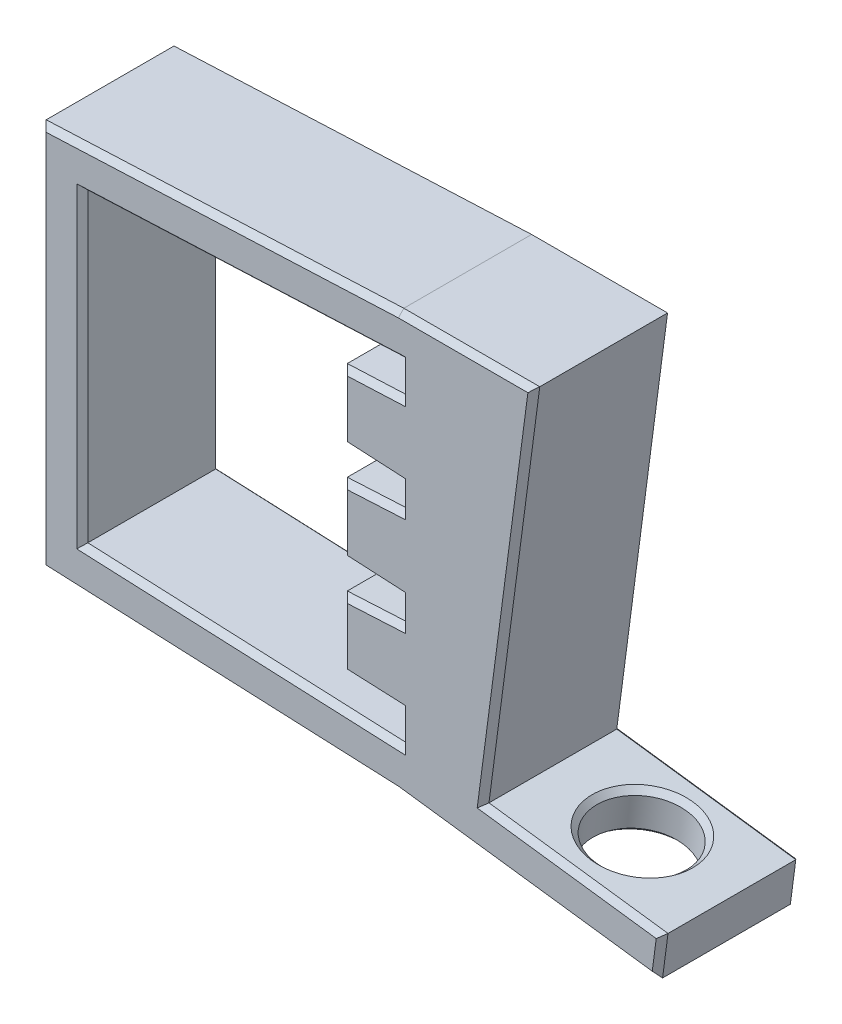
SolidWorks part; units mm, degrees
ref_plane "Top" through (0, 0, 0) normal (0, 0, 1) x (1, 0, 0)
ref_plane "Front" through (0, 0, 0) normal (0, 1, 0) x (1, 0, 0)
ref_plane "Right" through (0, 0, 0) normal (1, 0, 0) x (0, 0, -1)
sketch "Sketch1" plane through (0, 0, 0) normal (0, 0, 1) x (1, 0, 0)
  line L0 (0, 0) -> (22.8782, -0.9989)
  line L1 (-3, -2.8719) -> (22.7473, -3.996)
  line L2 (0, 0) -> (0, 22)
  line L3 (0, 22) -> (22.8782, 22.9989)
  line L4 (-3, -2.8719) -> (-3, 24.8719)
  line L5 (-3, 24.8719) -> (22.7473, 25.996)
  line L9 (22.8782, -0.9989) -> (22.8782, 1.3011)
  line L10 (22.8782, 1.3011) -> (18.6782, 1.4845)
  line L11 (18.6782, 1.4845) -> (18.6782, 6.3347)
  line L12 (18.6782, 6.3347) -> (22.8782, 6.5548)
  line L13 (22.8782, 6.5548) -> (22.8782, 8.3548)
  line L14 (22.8782, 8.3548) -> (18.6782, 8.5749)
  line L15 (18.6782, 8.5749) -> (18.6782, 13.4251)
  line L20 (22.8782, 22.9989) -> (22.8782, 20.6989)
  line L21 (22.8782, 20.6989) -> (18.6782, 20.5155)
  line L22 (18.6782, 20.5155) -> (18.6782, 15.6653)
  line L23 (18.6782, 15.6653) -> (22.8782, 15.4452)
  line L24 (22.8782, 15.4452) -> (22.8782, 13.6452)
  line L25 (22.8782, 13.6452) -> (18.6782, 13.4251)
  line L26 (22.7473, -3.996) -> (41.3754, -6.4485)
  line L27 (41.3754, -6.4485) -> (41.767, -3.4741)
  line L28 (41.767, -3.4741) -> (28.8782, -1.7773)
  line L29 (28.8782, -1.7773) -> (32.5346, 25.996)
  line L30 (32.5346, 25.996) -> (22.7473, 25.996)
  point P3 (0, 0)
  dimension "D1" = 92.5
  dimension "D2" = 92.5
  dimension "D3" = 22
  dimension "D4" = 22.9
  dimension "D6" = 90
  dimension "D8" = 92.5
  dimension "D9" = 93
  dimension "D10" = 93
  dimension "D11" = 1.8
  dimension "D12" = 2.3
  dimension "D13" = 3
  dimension "D14" = 13
  dimension "D15" = 82.5
  dimension "D16" = 2.3
  dimension "D17" = 1.8
  dimension "D18" = 6
  dimension "D19" = 4.2
  dimension "D5" = 3
extrude "Boss-Extrude1" add sketch "Sketch1" along normal blind 10
sketch "Sketch2" plane through (-2.6361, 2.3717, 0) normal (0.1305, 0.9914, 0) x (0.9914, -0.1305, 0)
  line L0 (31.7863, -10) -> (31.7863, 0) construction
  line L3 (25.9975, 0) -> (44.7863, 0) construction
  circle A1 centre (38.2863, -5) radius 3.25
  dimension "D3" = 6.5
  dimension "D1" = 5
  dimension "D2" = 6.5
extrude "Cut-Extrude1" cut sketch "Sketch2" against normal blind 10
chamfer "Chamfer1" distance 0.4 angle 45 50 edges at (22.8782, 0.1511, 10) (20.7782, 1.3928, 10) (18.6782, 3.9096, 10) (20.7782, 6.4447, 10) (22.8782, 7.4548, 10) (20.7782, 8.4648, 10) (18.6782, 11, 10) (20.7782, 13.5352, 10) (22.8782, 14.5452, 10) (20.7782, 15.5553, 10) (18.6782, 18.0904, 10) (20.7782, 20.6072, 10) (22.8782, 21.8489, 10) (11.4391, 22.4994, 10) (0, 11, 10) (11.4391, -0.4994, 10) (9.8737, 25.434, 10) (27.641, 25.996, 10) (30.7064, 12.1094, 10) (35.3226, -2.6257, 10) (41.5712, -4.9613, 10) (32.0614, -5.2222, 10) (9.8737, -3.434, 10) (-3, 11, 10) (11.4391, 22.4994, 0) (22.8782, 21.8489, 0) (20.7782, 20.6072, 0) (18.6782, 18.0904, 0) (20.7782, 15.5553, 0) (22.8782, 14.5452, 0) (20.7782, 13.5352, 0) (18.6782, 11, 0) (20.7782, 8.4648, 0) (22.8782, 7.4548, 0) (20.7782, 6.4447, 0) (18.6782, 3.9096, 0) (20.7782, 1.3928, 0) (22.8782, 0.1511, 0) (11.4391, -0.4994, 0) (0, 11, 0) (9.8737, -3.434, 0) (32.0614, -5.2222, 0) (41.5712, -4.9613, 0) (35.3226, -2.6257, 0) (30.7064, 12.1094, 0) (27.641, 25.996, 0) (9.8737, 25.434, 0) (-3, 11, 0) (31.7088, -5.1758, 5) (32.1004, -2.2015, 5)
